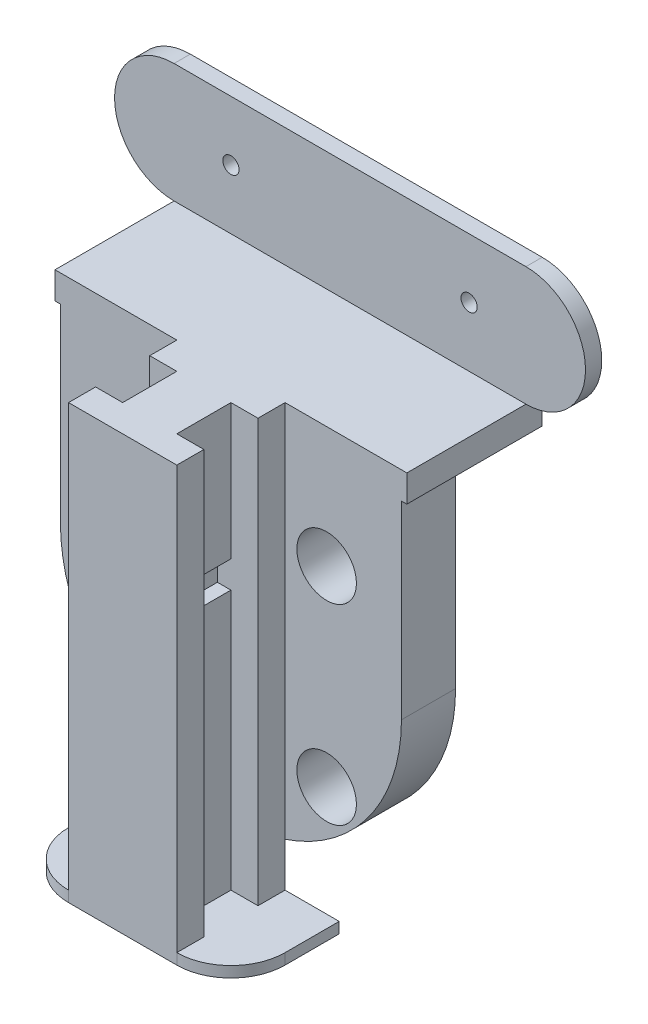
SolidWorks part; units mm, degrees
note: The reader was unsure of these and kept them because the rebuilt part matched: shared geometry of "Sketch1<3>", "Sketch1<4>".
ref_plane "Front Plane" through (0, 0, 0) normal (0, 0, 1) x (1, 0, 0)
ref_plane "Top Plane" through (0, 0, 0) normal (0, 1, 0) x (1, 0, 0)
ref_plane "Right Plane" through (0, 0, 0) normal (1, 0, 0) x (0, 0, -1)
sketch "Sketch1" plane through (0, 0, 0) normal (0, 0, 1) x (1, 0, 0)
  line L0 (0, 31.5) -> (0, 40)
  line L1 (0, 40) -> (-31.5, 40)
  line L2 (-31.5, 40) -> (-31.5, 0)
  line L3 (0, 40) -> (31.5, 40)
  line L4 (31.5, 40) -> (31.5, 0)
  line L5 (0, 0) -> (0, 58.2452) construction
  line L6 (0, 0) -> (-17.6777, 17.6777) construction
  line L7 (0, 0) -> (17.6777, 17.6777) construction
  line L8 (0, 0) -> (-31.5, 0) construction
  line L9 (0, 0) -> (17.6777, -17.6777) construction
  circle A0 centre (0, 0) radius 31.5
  circle A1 centre (0, 0) radius 25
  circle A2 centre (-17.6777, 17.6777) radius 2.5
  circle A3 centre (17.6777, 17.6777) radius 2.5
  circle A4 centre (0, 25) radius 2.5
  circle A5 centre (17.6777, -17.6777) radius 2.5
  circle A6 centre (-17.6777, -17.6777) radius 2.5
  circle A8 centre (-17.6777, 17.6777) radius 5.5
  circle A9 centre (17.6777, 17.6777) radius 5.5
  circle A10 centre (-17.6777, -17.6777) radius 5.5
  circle A11 centre (17.6777, -17.6777) radius 5.5
  dimension "D1" = 63
  dimension "D3" = 50
  dimension "D4" = 5
  dimension "D7" = 5
  dimension "D8" = 5
  dimension "D9" = 11
  dimension "D10" = 11
  dimension "D11" = 11
  dimension "D12" = 11
  dimension "D2" = 40
  dimension "D5" = 45
  dimension "D6" = 45
extrude "Boss-Extrude1" add sketch "Sketch1" along normal blind 10 contours A11 A1 A9 A4 A8 A10 | A0 A11 A1 A10 A8 A4 A9 | A0 L4 L3 L0 | A0 L0 L1 L2 | A1 A4
sketch "Sketch2" plane through (0, 40, 0) normal (0, 1, 0) x (1, 0, 0)
  line L9 (31.5, -10) -> (32.5, -10)
  line L15 (32.5, -10) -> (-32.5, -10)
  line L16 (32.5, -10) -> (32.5, 15)
  line L17 (32.5, 15) -> (-32.5, 15)
  line L18 (-32.5, -10) -> (-32.5, 15)
  dimension "D1" = 25
  dimension "D2" = 65
  dimension "D3" = 1
extrude "Boss-Extrude2" add sketch "Sketch1<3>" along normal blind 2 contours A1 A8 A2 | A1 A8 A2 | A1 A10 A6 | A1 A10 A6 | A1 A11 A5 | A1 A11 A5 | A9 A1 A3 | A1 A9 A3 | A1 A4 | A1 A4
sketch "Sketch1<3>" plane through (0, 0, 0) normal (0, 0, 1) x (1, 0, 0) same geometry as "Sketch1"
extrude "Boss-Extrude3" add sketch "Sketch1<4>" against normal blind 5 contours A1 A4 | A1 A4
sketch "Sketch1<4>" plane through (0, 0, 0) normal (0, 0, 1) x (1, 0, 0) same geometry as "Sketch1"
extrude "Boss-Extrude4" add sketch "Sketch2" against normal blind 5
sketch "Sketch4" plane through (0, 0, 10) normal (0, 0, 1) x (1, 0, 0)
  line L0 (-32.5, 40) -> (32.5, 40) construction
  line L1 (-10, -40) -> (10, -40)
  line L2 (-10, -40) -> (-10, 40)
  line L3 (-10, 40) -> (10, 40)
  line L4 (10, -40) -> (10, 40)
  line L5 (0, 40) -> (0, -40) construction
  line L6 (-10, 0) -> (10, 0) construction
  point P0 (0, 0)
  dimension "D1" = 20
extrude "Boss-Extrude5" add sketch "Sketch4" along normal blind 20
sketch "Sketch5" plane through (10, 0, 0) normal (1, 0, 0) x (0, 0, -1)
  line L0 (-10, -40) -> (-10, -29.8706) construction
  line L1 (-30, -40) -> (-10, -40)
  line L2 (-30, -40) -> (-30, -38)
  line L3 (-30, -38) -> (-10, -38)
  line L4 (-10, -40) -> (-10, -38)
  dimension "D1" = 2
extrude "Boss-Extrude6" add sketch "Sketch5" along normal blind 10 and the other way blind 30
sketch "Sketch7" plane through (0, 40, 0) normal (0, 1, 0) x (1, 0, 0)
  line L0 (-10, -25) -> (-5, -25)
  line L1 (-10, -30) -> (-10, -10) construction
  line L2 (-5, -25) -> (-5, -15)
  line L3 (-5, -15) -> (-10, -15)
  line L4 (10, -30) -> (-10, -30) construction
  line L5 (0, 0) -> (0, -30) construction
  line L6 (5, -15) -> (10, -15)
  line L7 (5, -25) -> (5, -15)
  line L8 (10, -25) -> (5, -25)
  line L9 (-10, -25) -> (-10, -15)
  line L10 (10, -25) -> (10, -15)
  dimension "D1" = 10
  dimension "D2" = 5
  dimension "D3" = 5
extrude "Cut-Extrude1" cut sketch "Sketch7" against normal blind 78
fillet "Fillet1" radius 10 2 edges at (-20, -39, 30) (20, -39, 30)
sketch "Sketch9" plane through (5, 0, 0) normal (1, 0, 0) x (0, 0, -1)
  line L0 (-25, -38) -> (-25, 40) construction
  line L1 (-25, 15) -> (-15, 15)
  line L2 (-25, 15) -> (-25, 10)
  line L3 (-25, 10) -> (-15, 10)
  line L4 (-15, 15) -> (-15, 10)
  line L5 (-15, -38) -> (-15, 40) construction
  line L6 (-15, 40) -> (-25, 40) construction
  dimension "D1" = 5
  dimension "D2" = 25
extrude "Cut-Extrude2" cut sketch "Sketch9" against normal blind 2.5
sketch "Sketch14" plane through (0, 0, -15) normal (0, 0, -1) x (-1, 0, 0)
  line L0 (-32.5, 40) -> (32.5, 40) construction
  line L1 (-32.5, 40) -> (32.5, 40)
  line L2 (0, 0) -> (0, 51) construction
  line L3 (32.5, 51) -> (-32.5, 51) construction
  line L4 (32.5, 40) -> (-32.5, 40)
  line L5 (32.5, 62) -> (-32.5, 62)
  arc A0 (32.5, 40) -> (32.5, 62) centre (32.5, 51) ccw
  arc A1 (-32.5, 62) -> (-32.5, 40) centre (-32.5, 51) ccw
  circle A2 centre (-22, 51) radius 1.5
  circle A3 centre (22, 51) radius 1.5
  point P7 (0, 51)
  line M4 (32.5, 40) -> (-32.5, 40)
  dimension "D1" = 11
  dimension "D4" = 22
  dimension "D5" = 3
  dimension "D2" = 0
  dimension "D3" = 65
extrude "Boss-Extrude8" add sketch "Sketch14" against normal blind 3 contours L5 A1 A0 A2 A3 M4
sketch "Sketch15" plane through (0, 0, -15) normal (0, 0, -1) x (-1, 0, 0)
  line L0 (32.5, 40) -> (-32.5, 40) construction
  circle A0 centre (22, 51) radius 1.5 construction
  circle A1 centre (-22, 51) radius 1.5 construction
  circle A2 centre (22, 51) radius 1.5
  circle A3 centre (-22, 51) radius 1.5
  circle A4 centre (-22, 51) radius 1.5
  circle A5 centre (22, 51) radius 1.5
  point P10 (0, 0)
  point P11 (22, 51)
  dimension "D1" = 3
  dimension "D2" = 3
  dimension "D3" = 11
sketch "Sketch16" plane through (-5, 0, 0) normal (-1, 0, 0) x (0, 0, 1)
  line L0 (15, -38) -> (15, 40) construction
  line L1 (15, 15) -> (25, 15)
  line L2 (15, 15) -> (15, 10)
  line L3 (15, 10) -> (25, 10)
  line L4 (25, 15) -> (25, 10)
  line L5 (25, -38) -> (25, 40) construction
  line L6 (25, 40) -> (15, 40) construction
  dimension "D1" = 5
  dimension "D2" = 25
extrude "Cut-Extrude4" cut sketch "Sketch16" against normal blind 2.5
